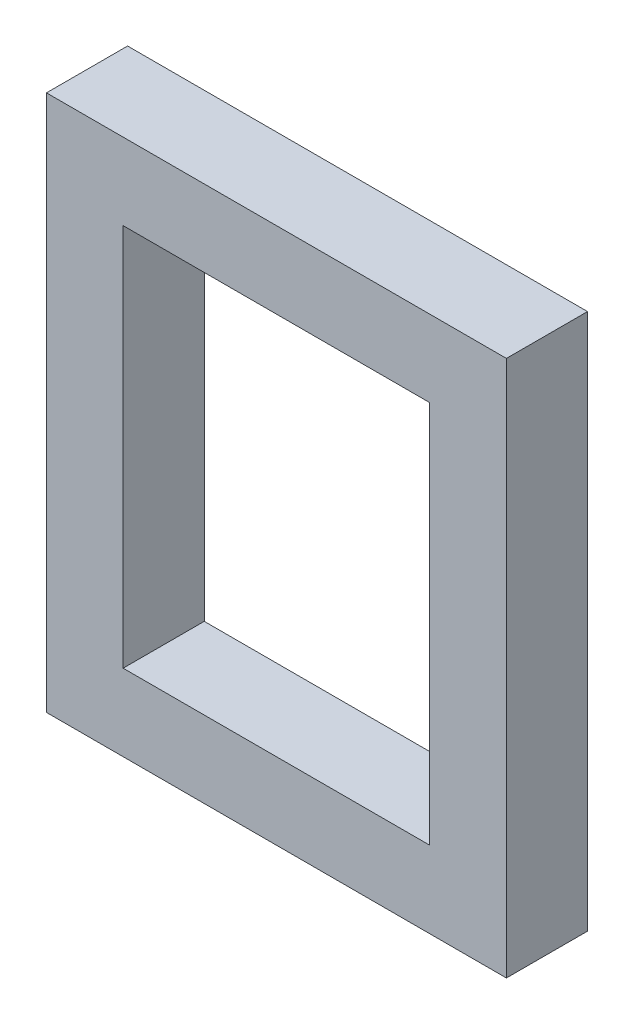
SolidWorks part; units mm, degrees
material "EPDM"
ref_plane "Front Plane" through (0, 0, 0) normal (0, 0, 1) x (1, 0, 0)
ref_plane "Top Plane" through (0, 0, 0) normal (0, 1, 0) x (1, 0, 0)
ref_plane "Right Plane" through (0, 0, 0) normal (1, 0, 0) x (0, 0, -1)
sketch "Sketch1" plane through (0, 0, 0) normal (0, 0, 1) x (1, 0, 0)
  line L1 (-9, -10.5) -> (9, -10.5)
  line L2 (-9, -10.5) -> (-9, 10.5)
  line L3 (-9, 10.5) -> (9, 10.5)
  line L4 (9, -10.5) -> (9, 10.5)
  line L5 (-9, -10.5) -> (9, 10.5) construction
  line L6 (-9, 10.5) -> (9, -10.5) construction
  line L7 (-6, -7.5) -> (6, -7.5)
  line L8 (-6, -7.5) -> (-6, 7.5)
  line L9 (-6, 7.5) -> (6, 7.5)
  line L10 (6, -7.5) -> (6, 7.5)
  line L11 (-6, -7.5) -> (6, 7.5) construction
  line L12 (-6, 7.5) -> (6, -7.5) construction
  point P0 (0, 0)
  point P6 (0, 0)
  dimension "D1" = 3
  dimension "D2" = 18
  dimension "D3" = 21
  dimension "D4" = 3
extrude "Boss-Extrude1" add sketch "Sketch1" along normal blind 3.175
